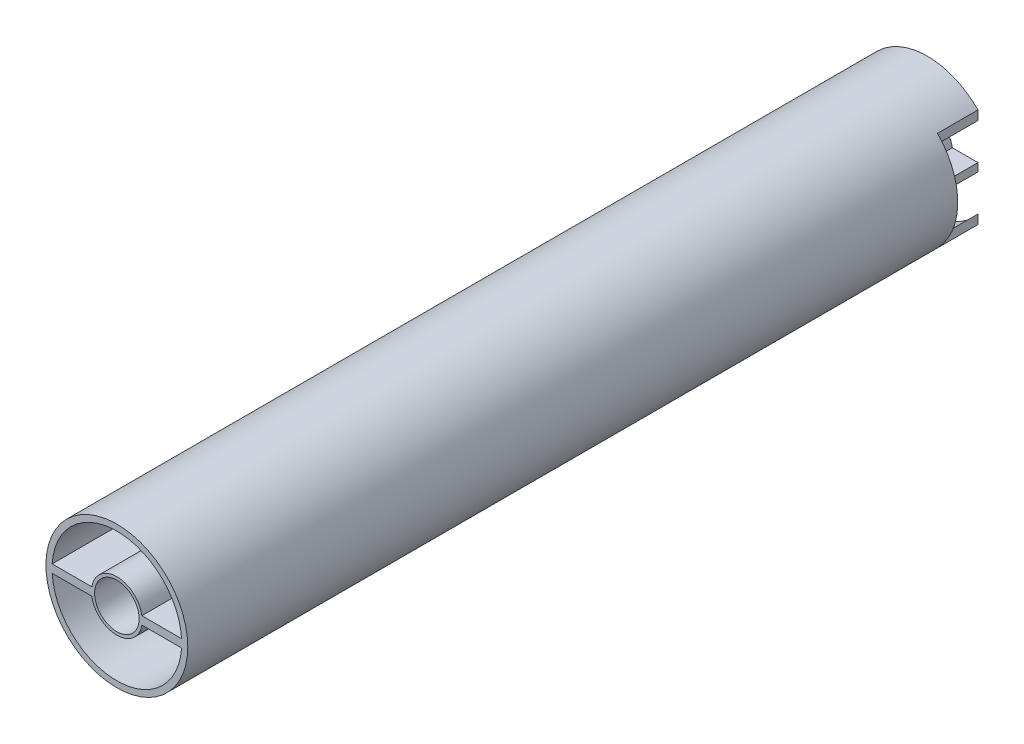
SolidWorks part; units mm, degrees
note: The reader was unsure of these and kept them because the rebuilt part matched: shared geometry of "Sketch2<18>".
ref_plane "Front Plane" through (0, 0, 0) normal (0, 0, 1) x (1, 0, 0)
ref_plane "Top Plane" through (0, 0, 0) normal (0, 1, 0) x (1, 0, 0)
ref_plane "Right Plane" through (0, 0, 0) normal (1, 0, 0) x (0, 0, -1)
sketch "Sketch2" plane through (0, 0, 0) normal (0, 0, 1) x (1, 0, 0)
  line L0 (-16, 0) -> (0, 0) construction
  line L1 (12.5, 12.2474) -> (12.5, -12.2474)
  line L2 (6.1695, 1) -> (15.9687, 1)
  line L3 (-12.5, 12.2474) -> (-12.5, -12.2474)
  line L4 (0, 16) -> (0, -16) construction
  line L6 (6.1695, -1) -> (15.9687, -1)
  line L7 (-15.9687, -1) -> (-6.1695, -1)
  line L9 (-15.9687, 1) -> (-6.1695, 1)
  line L10 (-12.5, -9.9875) -> (-12.5, -12.2474)
  line L12 (12.5, -9.9875) -> (12.5, -12.2474)
  line L13 (5.5, 0) -> (16, 0) construction
  circle A8 centre (0, 0) radius 17.5
  circle A10 centre (0, 0) radius 16
  arc A11 (-6.1695, -1) -> (6.1695, -1) centre (0, 0) ccw
  circle A12 centre (0, 0) radius 5.5
  arc A13 (6.1695, 1) -> (-6.1695, 1) centre (0, 0) ccw
  point P8 (-12.5, 0)
  point P17 (12.5, 0)
  dimension "D1" = 35
  dimension "D2" = 32
  dimension "D3" = 12.5
  dimension "D6" = 12.5
  dimension "D5" = 1
  dimension "D4" = 11
extrude "Shell" add sketch "Sketch2" along normal blind 200
ref_plane "Plane2" through (0, 0, 150) normal (0, 0, 1) x (1, 0, 0)
sketch "Sketch13" plane through (0, 0, 150) normal (0, 0, 1) x (1, 0, 0)
  line L0 (0, 6.25) -> (0, 11.125) construction
  line L1 (-5.5, 0) -> (5.5, 0) construction
  line L2 (0, -11.125) -> (0, -5.5) construction
  circle A0 centre (0, 0) radius 5.5
  circle A1 centre (0, 0) radius 6.25
  circle A2 centre (0, 0) radius 16
  circle A3 centre (0, 11.125) radius 4
  circle A4 centre (0, -11.125) radius 4
  dimension "D1" = 11
  dimension "D2" = 12.5
  dimension "D3" = 32
  dimension "D5" = 8
  dimension "D4" = 4.875
extrude "InnerPartition" add sketch "Sketch13" along normal mid plane 5 contours A2 A1 A3 A4
extrude "EasierAssembly_ShellStuds" cut sketch "Sketch2<18>" along normal blind 10 contours L2 A10 L1 | L3 A10 L9 | L7 A10 L3 | L1 A10 L6 | L6 A10 L2 L1 | L9 A10 L7 L3 | A10 L3 A8 | A10 L1 A8
sketch "Sketch2<18>" plane through (0, 0, 0) normal (0, 0, 1) x (1, 0, 0) same geometry as "Sketch2"
